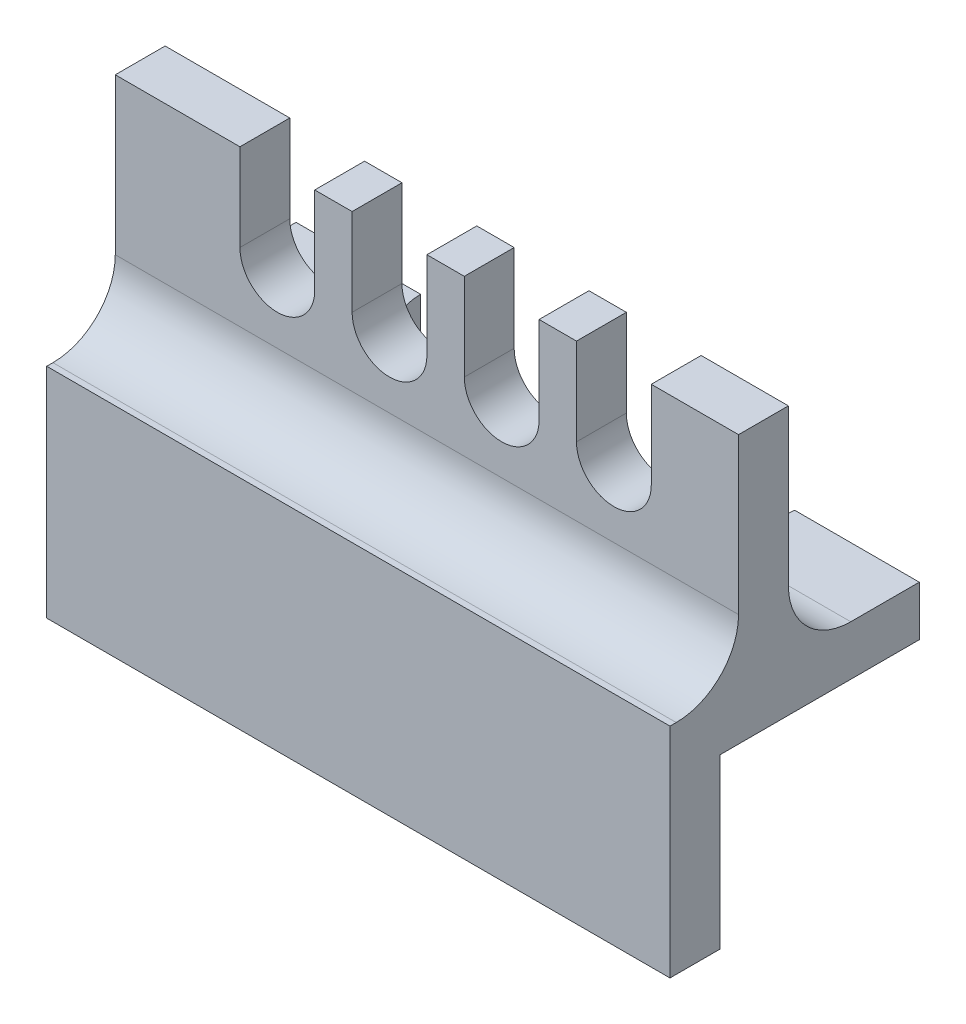
SolidWorks part; units mm, degrees
ref_plane "Front Plane" through (0, 0, 0) normal (0, 0, 1) x (1, 0, 0)
ref_plane "Top Plane" through (0, 0, 0) normal (0, 1, 0) x (1, 0, 0)
ref_plane "Right Plane" through (0, 0, 0) normal (1, 0, 0) x (0, 0, -1)
sketch "Sketch1" plane through (0, 0, 0) normal (1, 0, 0) x (0, 0, -1)
  line L0 (0, 0) -> (0, 35)
  line L1 (0, 35) -> (11, 35)
  line L2 (11, 35) -> (11, 70)
  line L3 (11, 70) -> (19, 70)
  line L4 (19, 70) -> (19, 35)
  line L5 (19, 35) -> (40, 35)
  line L6 (40, 35) -> (40, 27)
  line L7 (40, 27) -> (8, 27)
  line L8 (8, 27) -> (8, 0)
  line L9 (8, 0) -> (0, 0)
  point P3 (0, 0)
  dimension "D1" = 8
  dimension "D2" = 27
  dimension "D3" = 8
  dimension "D4" = 35
  dimension "D5" = 70
  dimension "D6" = 21
  dimension "D7" = 40
extrude "Boss-Extrude1" add sketch "Sketch1" against normal blind 100
fillet "Fillet1" radius 10 2 edges at (-50, 35, -11) (-50, 35, -19)
sketch "Sketch4" plane through (0, 0, -40) normal (0, 0, -1) x (-1, 0, 0)
  line L0 (20, 35) -> (80, 35)
  line L1 (100, 35) -> (0, 35) construction
  line L2 (80, 35) -> (80, 27)
  line L3 (100, 27) -> (0, 27) construction
  line L4 (80, 27) -> (20, 27)
  line L5 (20, 27) -> (20, 35)
  line L6 (100, 27) -> (100, 35) construction
  dimension "D1" = 20
  dimension "D2" = 60
extrude "Cut-Extrude1" cut sketch "Sketch4" against normal blind 10
fillet "Fillet2" radius 10 2 edges at (-20, 31, -30) (-80, 31, -30)
sketch "Sketch5" plane through (0, 0, -19) normal (0, 0, -1) x (-1, 0, 0)
  line L0 (0, 45) -> (0, 70) construction
  line L1 (100, 70) -> (0, 70) construction
  line L2 (14, 70) -> (14, 56)
  line L3 (14, 56) -> (26, 56)
  line L4 (26, 56) -> (26, 70)
  line L5 (26, 70) -> (14, 70)
  line L6 (32, 56) -> (44, 56)
  line L10 (44, 56) -> (44, 70)
  line L15 (68, 70) -> (68, 56)
  line L16 (68, 56) -> (80, 56)
  line L17 (80, 56) -> (80, 70)
  line L18 (80, 70) -> (68, 70)
  line L20 (32, 70) -> (32, 56)
  line L24 (44, 70) -> (32, 70)
  line L25 (50, 70) -> (50, 56)
  line L26 (50, 56) -> (62, 56)
  line L27 (62, 56) -> (62, 70)
  line L28 (62, 70) -> (50, 70)
  point P0 (20, 56)
  dimension "D1" = 20
  dimension "D2" = 12
  dimension "D3" = 6
  dimension "D4" = 12
  dimension "D5" = 6
  dimension "D6" = 12
  dimension "D7" = 14
  dimension "D8" = 14
  dimension "D9" = 14
  dimension "D10" = 6
  dimension "D11" = 12
  dimension "D12" = 14
extrude "Cut-Extrude2" cut sketch "Sketch5" against normal blind 10
sketch "Sketch6" plane through (0, 0, -19) normal (0, 0, -1) x (-1, 0, 0)
  line L0 (14, 58.5787) -> (14, 56)
  line L1 (14, 70) -> (14, 56) construction
  line L2 (26, 56) -> (26, 58.5787)
  line L3 (26, 56) -> (26, 70) construction
  line L4 (26, 58.5787) -> (14, 58.5787)
  line L5 (32, 56) -> (32, 58.5787)
  line L6 (32, 70) -> (32, 56) construction
  line L7 (32, 58.5787) -> (44, 58.5787)
  line L8 (44, 56) -> (44, 70) construction
  line L9 (44, 58.5787) -> (44, 56)
  line L10 (50, 56) -> (50, 58.5787)
  line L11 (50, 70) -> (50, 56) construction
  line L12 (50, 58.5787) -> (62, 58.5787)
  line L13 (62, 56) -> (62, 70) construction
  line L14 (62, 58.5787) -> (62, 56)
  line L15 (68, 56) -> (68, 58.5787)
  line L16 (68, 70) -> (68, 56) construction
  line L17 (68, 58.5787) -> (80, 58.5787)
  line L18 (80, 56) -> (80, 70) construction
  line L19 (80, 58.5787) -> (80, 56)
  arc A0 (14, 56) -> (26, 56) centre (20, 56) ccw
  arc A1 (44, 56) -> (32, 56) centre (38, 56) cw
  arc A2 (62, 56) -> (50, 56) centre (56, 56) cw
  arc A3 (80, 56) -> (68, 56) centre (74, 56) cw
extrude "Cut-Extrude3" cut sketch "Sketch6" against normal blind 10
